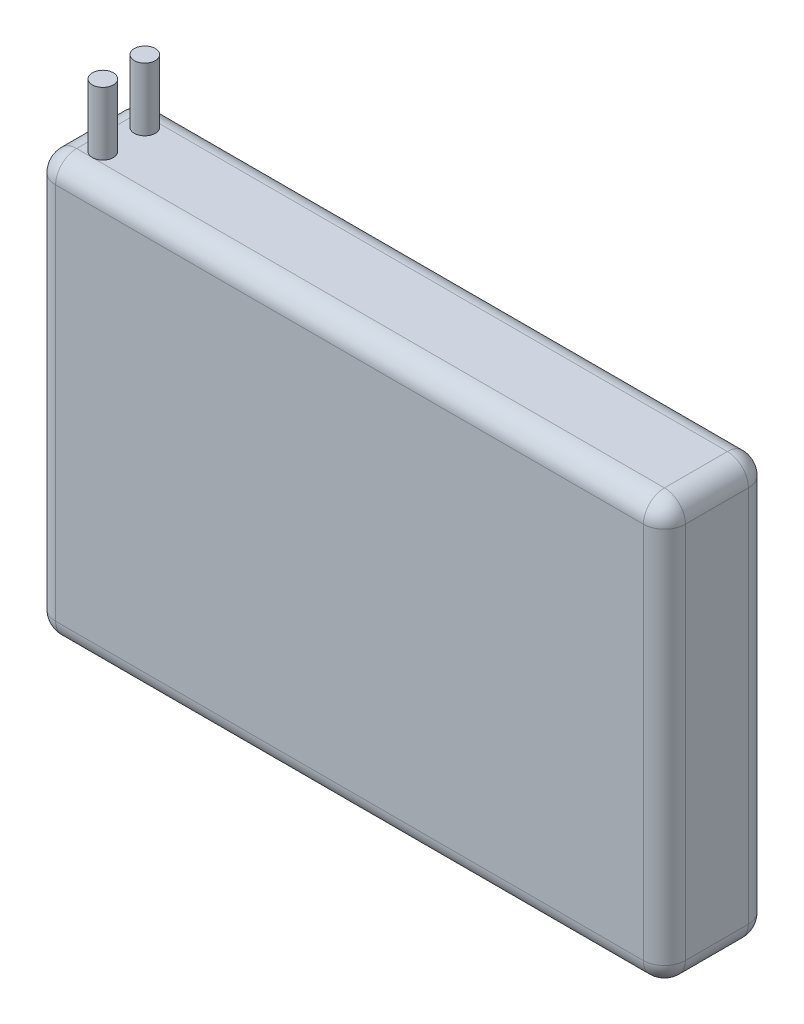
SolidWorks part; units mm, degrees
ref_plane "Front Plane" through (0, 0, 0) normal (0, 0, 1) x (1, 0, 0)
ref_plane "Top Plane" through (0, 0, 0) normal (0, 1, 0) x (1, 0, 0)
ref_plane "Right Plane" through (0, 0, 0) normal (1, 0, 0) x (0, 0, -1)
sketch "Sketch1" plane through (0, 0, 0) normal (0, 0, 1) x (1, 0, 0)
  line L1 (-15, -10) -> (15, -10)
  line L2 (-15, -10) -> (-15, 10)
  line L3 (-15, 10) -> (15, 10)
  line L4 (15, -10) -> (15, 10)
  line L5 (0, 10) -> (0, -10) construction
  line L6 (-15, 0) -> (15, 0) construction
  point P0 (0, 0)
  dimension "D1" = 30
  dimension "D2" = 20
extrude "Boss-Extrude1" add sketch "Sketch1" along normal mid plane 5
fillet "Fillet1" radius 1 12 edges at (15, 10, 0) (-15, 10, 0) (-15, -10, 0) (15, -10, 0) (0, -10, 2.5) (-15, 0, 2.5) (0, 10, 2.5) (15, 0, 2.5) (0, -10, -2.5) (-15, 0, -2.5) (0, 10, -2.5) (15, 0, -2.5)
sketch "Sketch3" plane through (0, 10, 0) normal (0, 1, 0) x (1, 0, 0)
  line L0 (-23.5, 0) -> (-21.2148, 0) construction
  line L3 (-14, 1.5) -> (-14, -1.5) construction
  circle A0 centre (-13.25, 1) radius 0.5
  circle A2 centre (-13.25, -1) radius 0.5
  dimension "D1" = 0.75
  dimension "D3" = 1
  dimension "D2" = 1
extrude "Boss-Extrude2" add sketch "Sketch3" along normal blind 3 from surface starting at face at (0, 10, 0)
sketch "Sketch5" plane through (0, 0, 2.5) normal (0, 0, 1) x (1, 0, 0)
  line L0 (-10.5373, 1.601) -> (23.5, 1.601) construction
  line L1 (-14.2977, -14) -> (-14.2977, 14) construction
  text T0 "BLY 502030 3.7V\r\n250mah 0.74Wh\r\n\r\n" font "Century Gothic" height 2
  dimension "D1" = 14.2977
wrap "Wrap1" sketch "Sketch5" wrap type scribe source sketch "Sketch5" face at (0, 0, -2.5)
